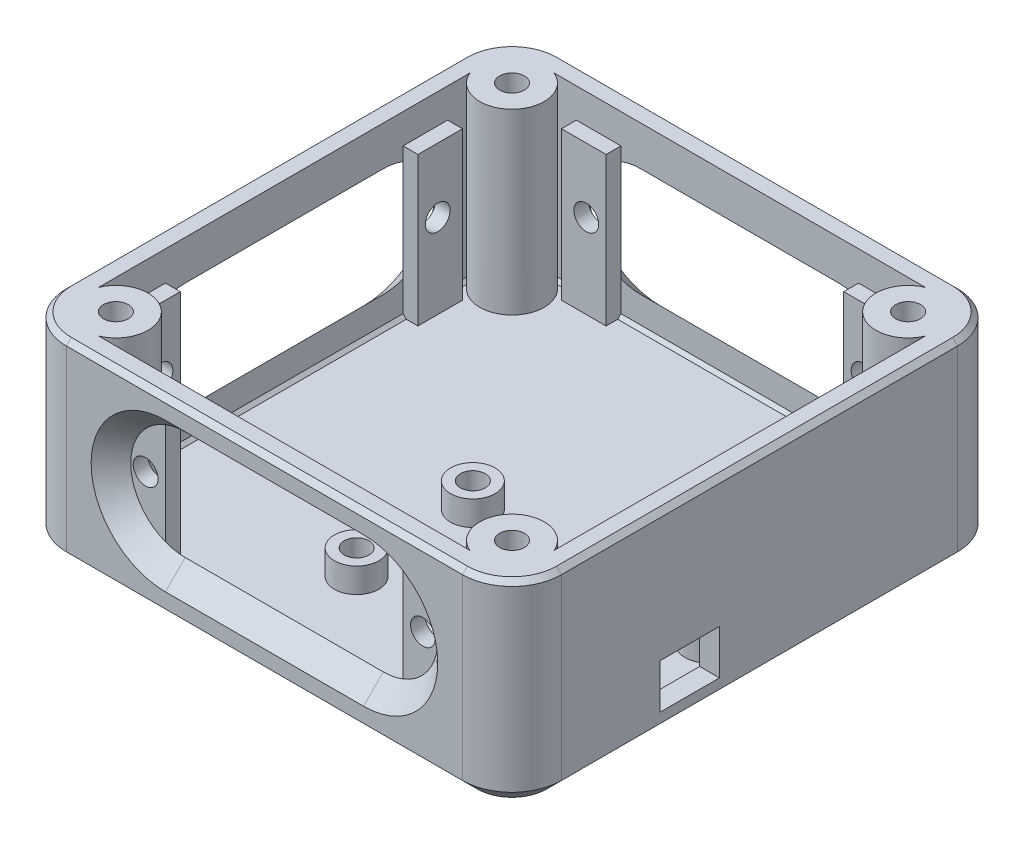
SolidWorks part; units mm, degrees
ref_plane "Plan de face" through (0, 0, 0) normal (0, 0, 1) x (1, 0, 0)
ref_plane "Plan de dessus" through (0, 0, 0) normal (0, 1, 0) x (1, 0, 0)
ref_plane "Plan de droite" through (0, 0, 0) normal (1, 0, 0) x (0, 0, -1)
sketch "Esquisse1" plane through (0, 0, 0) normal (0, 1, 0) x (1, 0, 0)
  line L1 (0, 0) -> (100, 0)
  line L2 (0, 0) -> (0, 100)
  line L3 (0, 100) -> (100, 100)
  line L4 (100, 0) -> (100, 100)
  dimension "D1" = 100
extrude "Boss.-Extru.1" add sketch "Esquisse1" along normal blind 40
fillet "Congé1" radius 10 4 edges at (100, 20, -100) (0, 20, -100) (0, 20, 0) (100, 20, 0)
chamfer "Chanfrein1" distance 3 angle 45 8 edges at (2.9289, 0, -97.0711) (0, 0, -50) (2.9289, 0, -2.9289) (50, 0, 0) (97.0711, 0, -2.9289) (100, 0, -50) (97.0711, 0, -97.0711) (50, 0, -100)
sketch "Esquisse4" plane through (0, 40, 0) normal (0, 1, 0) x (1, 0, 0)
  line L0 (50, 100) -> (50, 0) construction
  line L1 (90, 100) -> (10, 100) construction
  line L2 (10, 0) -> (90, 0) construction
  line L3 (100, 50) -> (0, 50) construction
  line L4 (100, 10) -> (100, 90) construction
  line L5 (0, 90) -> (0, 10) construction
  circle A0 centre (10, 90) radius 2.5
  circle A1 centre (10, 10) radius 2.5
  circle A2 centre (90, 10) radius 2.5
  circle A3 centre (90, 90) radius 2.5
  dimension "D1" = 5
extrude "Enlèv. mat.-Extru.1" cut sketch "Esquisse4" against normal blind 36
shell "Coque2" thickness 4 removed face at (90, 40, -92.5)
sketch "Esquisse5" plane through (0, 4, 0) normal (0, 1, 0) x (1, 0, 0)
  line L1 (96, 12.5) -> (96, 87.5) construction
  line L2 (12.5, 4) -> (87.5, 4) construction
  circle A0 centre (92, 24) radius 2.5
  circle A1 centre (92, 47.4737) radius 2.5
  circle A2 centre (44.6196, 47.4737) radius 2.5
  circle A3 centre (44.6196, 24) radius 2.5
  circle A4 centre (44.6196, 47.4737) radius 4.5
  circle A5 centre (44.6196, 24) radius 4.5
  circle A6 centre (92, 24) radius 4.5
  circle A7 centre (92, 47.4737) radius 4.5
  dimension "D2" = 5
  dimension "D1" = 2
  dimension "D3" = 47.3804
  dimension "D4" = 23.4737
  dimension "D5" = 4
  dimension "D6" = 20
extrude "Boss.-Extru.2" add sketch "Esquisse5" along normal blind 5
sketch "Esquisse6" plane through (100, 0, 0) normal (1, 0, 0) x (0, 0, -1)
  line L1 (29.9, 14) -> (41.9, 14)
  line L2 (29.9, 14) -> (29.9, 5)
  line L3 (29.9, 5) -> (41.9, 5)
  line L4 (41.9, 14) -> (41.9, 5)
  line L10 (10, 40) -> (10, 3) construction
  line L11 (10, 3) -> (90, 3) construction
  dimension "D1" = 12
  dimension "D2" = 9
  dimension "D3" = 19.9
  dimension "D4" = 2
extrude "Enlèv. mat.-Extru.2" cut sketch "Esquisse6" against normal blind 20 contours L1 L4 L3 L2
sketch "Esquisse7" plane through (0, 0, -100) normal (0, 0, -1) x (-1, 0, 0)
  line L0 (-30, 21) -> (-70, 21) construction
  line L1 (-30, 6) -> (-70, 6)
  line L2 (-30, 36) -> (-70, 36)
  line L3 (-90, 3) -> (-10, 3) construction
  line L4 (-90, 40) -> (-90, 3) construction
  arc A0 (-30, 6) -> (-30, 36) centre (-30, 21) ccw
  arc A1 (-70, 36) -> (-70, 6) centre (-70, 21) ccw
  point P2 (-50, 21)
  point P9 (-50, 3)
  dimension "D1" = 15
  dimension "D3" = 20
  dimension "D2" = 3
extrude "Enlèv. mat.-Extru.3" cut sketch "Esquisse7" against normal up to next (4 mm away) draft 45
ref_plane "Plan1" through (0, 0, -50) normal (0, 0, 1) x (1, 0, 0)
ref_plane "Plan2" through (50, 0, 0) normal (1, 0, 0) x (0, 0, -1)
ref_axis "Axe1" through (50, 1.2, -50) along (0, 1, 0)
sketch "Esquisse8" plane through (0, 4, 0) normal (0, 1, 0) x (1, 0, 0)
  line L0 (87.5, 96) -> (12.5, 96) construction
  line L1 (74, 93) -> (83, 93)
  line L2 (74, 93) -> (74, 96)
  line L3 (74, 96) -> (83, 96)
  line L4 (83, 93) -> (83, 96)
  dimension "D1" = 0
  dimension "D2" = 3
  dimension "D3" = 2
  dimension "D4" = 9
extrude "Boss.-Extru.6" add sketch "Esquisse8" along direction (0, -1, 0) on the side of the normal blind 30
sketch "Esquisse9" plane through (0, 0, -96) normal (0, 0, -1) x (-1, 0, 0)
  line L0 (-74, 31.247) -> (-74, 10.753) construction
  circle A0 centre (-78, 21) radius 2.5
  point P4 (-74, 21)
  dimension "D1" = 5
  dimension "D2" = 4
extrude "Enlèv. mat.-Extru.4" cut sketch "Esquisse9" against normal blind 3.5
mirror "Symétrie1" about plane through (50, 0, 0) normal (1, 0, 0) of "Enlèv. mat.-Extru.4", "Boss.-Extru.6"
pattern_circular "Répétition circulaire1" count 3 every 90 about axis through (50, 1.2, -50) along (0, 1, 0) of "Enlèv. mat.-Extru.3", "Symétrie1"
sketch "Esquisse11" plane through (100, 0, 0) normal (1, 0, 0) x (0, 0, -1)
  line L0 (60, 3) -> (63, 0)
  line L1 (10, 3) -> (90, 3) construction
  line L2 (63, 0) -> (87, 0)
  line L3 (87, 0) -> (90, 3)
  line L4 (90, 3) -> (60, 3)
  dimension "D1" = 30
  dimension "D2" = 10
  dimension "D3" = 45
extrude "Enlèv. mat.-Extru.5" cut sketch "Esquisse11" against normal blind 97
chamfer "Chanfrein2" distance 1 angle 45 8 edges at (50, 40, -100) (2.9289, 40, -97.0711) (97.0711, 40, -97.0711) (0, 40, -50) (100, 40, -50) (2.9289, 40, -2.9289) (97.0711, 40, -2.9289) (50, 40, 0)
